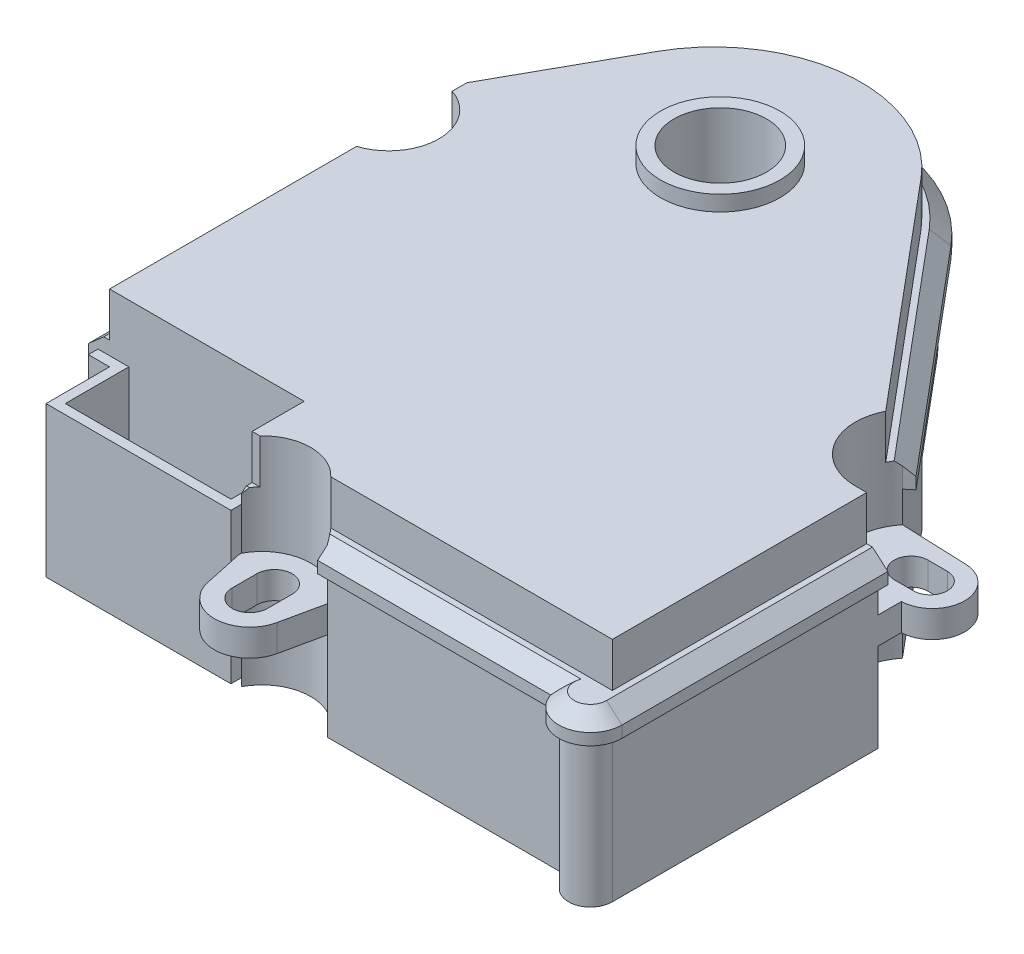
SolidWorks part; units mm, degrees
ref_plane "Front Plane" through (0, 0, 0) normal (0, 0, 1) x (1, 0, 0)
ref_plane "Top Plane" through (0, 0, 0) normal (0, 1, 0) x (1, 0, 0)
ref_plane "Right Plane" through (0, 0, 0) normal (1, 0, 0) x (0, 0, -1)
sketch "Sketch1" plane through (0, 0, 0) normal (0, 1, 0) x (1, 0, 0)
  line L0 (-34.65, 27.5) -> (-34.65, -27.5)
  line L1 (-34.65, -27.5) -> (34.65, -27.5)
  line L2 (40.35, -27.5) -> (40.35, 8.5)
  line L3 (40.35, 8.5) -> (8.1391, 46.8874)
  line L4 (-25.6622, 43.6579) -> (-34.65, 27.5)
  line L5 (-30.7563, 34.5) -> (18.5334, 34.5)
  line L6 (-7.65, 34.5) -> (-7.65, 54.25) construction
  circle A1 centre (-7.65, 34.5) radius 6
  circle A2 centre (-7.65, 34.5) radius 7.75
  arc A3 (40.35, -27.5) -> (34.65, -27.5) centre (37.5, -27.5) cw
  arc A4 (-25.6622, 43.6579) -> (8.1391, 46.8874) centre (-7.65, 33.6387) cw
  point P7 (0, -27.5)
  point P8 (-34.65, 0)
  dimension "D6" = 12
  dimension "D7" = 15.5
  dimension "D9" = 48
  dimension "D10" = 50
  dimension "D1" = 75
  dimension "D2" = 55
  dimension "D3" = 36
  dimension "D4" = 62
  dimension "D5" = 81.75
  dimension "D8" = 5.7
extrude "Boss-Extrude1" add sketch "Sketch1" along normal blind 28 contours A2 L6 A4 L4 L5 | L6 A2 L5 L3 A4 | A3 L2 L3 L5 A2 L4 L0 L1 region at (1.2938, 0, -1.2172) region at (-6.9972, 0, -43.3855)
extrude "Boss-Extrude2" add sketch "Sketch1<3>" along normal blind 2 and the other way up to surface from surface contours L6 A1 L5 A2 | L5 A2 A1 | A1 L6 A2 L5 region at (-12.0504, 0, -38.9004) region at (-14.525, 0, -34.3267) region at (-3.2496, 0, -38.9004) other way up to face at (3.954, 0, -7.1542) starting at face at (3.954, 28, -7.1542)
sketch "Sketch1<3>" plane through (0, 0, 0) normal (0, 1, 0) x (1, 0, 0) same geometry as "Sketch1"
extrude "Boss-Extrude3" add sketch "Sketch1<4>" against normal blind 6 contours L6 A1 L5 A2 | A1 L6 A2 L5 | L5 A2 A1 region at (-12.0504, 0, -38.9004) region at (-14.525, 0, -34.3267) region at (-3.2496, 0, -38.9004)
sketch "Sketch1<4>" plane through (0, 0, 0) normal (0, 1, 0) x (1, 0, 0) same geometry as "Sketch1"
extrude "Cut-Extrude1" cut sketch "Sketch1<5>" along normal blind 8 contours A2 L6 A4 L4 L5 | L6 A2 L5 L3 A4 region at (-6.9972, 0, -43.3855)
sketch "Sketch1<5>" plane through (0, 0, 0) normal (0, 1, 0) x (1, 0, 0) same geometry as "Sketch1"
sketch "Sketch6" plane through (0, 28, 0) normal (0, 1, 0) x (1, 0, 0)
  line L9 (38.85, -26) -> (38.85, 7.954)
  line L10 (38.85, 7.954) -> (6.9901, 45.9232)
  line L11 (-24.3514, 42.9288) -> (-33.15, 27.1109)
  line L12 (-33.15, 27.1109) -> (-33.15, -26)
  line L13 (-33.15, -26) -> (33.7821, -26)
  line L14 (-26.5361, 44.1441) -> (-35.65, 27.7594)
  line L15 (-35.65, 27.7594) -> (-35.65, -28.5)
  line L16 (-35.65, -28.5) -> (33.7821, -28.5)
  line L17 (41.35, -27.5) -> (41.35, 8.864)
  line L18 (41.35, 8.864) -> (8.9052, 47.5302)
  line L19 (-26.5361, 44.1441) -> (-35.65, 27.7594)
  line L20 (-35.65, 27.7594) -> (-35.65, -28.5)
  line L21 (-35.65, -28.5) -> (33.7821, -28.5)
  line L22 (41.35, -27.5) -> (41.35, 8.864)
  line L23 (41.35, 8.864) -> (8.9052, 47.5302)
  line L24 (-24.3514, 42.9288) -> (-33.4652, 26.5441) construction
  line L25 (-33.15, 27.7594) -> (-33.15, -26) construction
  line L26 (33.7821, -26) -> (38.85, -26)
  line L27 (38.85, -27.5) -> (38.85, 7.954) construction
  arc A3 (6.9901, 45.9232) -> (-24.3514, 42.9288) centre (-7.65, 33.6387) ccw
  arc A4 (8.9052, 47.5302) -> (-26.5361, 44.1441) centre (-7.65, 33.6387) ccw
  arc A5 (33.7821, -28.5) -> (41.35, -27.5) centre (37.5, -27.5) ccw
  arc A6 (8.9052, 47.5302) -> (-26.5361, 44.1441) centre (-7.65, 33.6387) ccw
  arc A7 (33.7821, -28.5) -> (41.35, -27.5) centre (37.5, -27.5) ccw
  arc A10 (36.1963, -27.8506) -> (38.85, -27.5) centre (37.5, -27.5) ccw construction
  dimension "D2" = 2.5
  dimension "D3" = 2.5
  dimension "D1" = 1
sketch "Sketch2" plane through (0, 28, 0) normal (0, 1, 0) x (1, 0, 0)
  line L0 (-34.65, -27.5) -> (34.65, -27.5) construction
  line L1 (40.35, -27.5) -> (40.35, 8.5) construction
  line L2 (-7.95, -27.5) -> (-6.7974, -32.866)
  line L3 (2.1974, -32.866) -> (3.35, -27.5)
  line L4 (-4.6, -28.7) -> (-4.6, -31.9)
  line L5 (0, -31.9) -> (0, -28.7)
  arc A1 (-6.7974, -32.866) -> (2.1974, -32.866) centre (-2.3, -31.9) ccw
  arc A2 (-4.6, -31.9) -> (0, -31.9) centre (-2.3, -31.9) ccw
  arc A3 (0, -28.7) -> (-4.6, -28.7) centre (-2.3, -28.7) ccw
  arc A4 (-7.95, -27.5) -> (3.35, -27.5) centre (-2.3, -30.3104) cw
  point P18 (-2.3, -26.4)
  point P19 (-2.3, -34.2)
  point P20 (-2.3, -36.5)
  point P21 (-2.3, -24)
  line M7 (-34.65, -27.5) -> (34.65, -27.5)
  dimension "D3" = 7.8
  dimension "D5" = 2.3
  dimension "D6" = 9
  dimension "D1" = 37
  dimension "D2" = 11.3
  dimension "D4" = 4.6
  dimension "D7" = 12.5
extrude "Cut-Extrude2" cut sketch "Sketch2" against normal through all contours A4 A3 M7 | A3 M7 region at (-2.3, 28, 25.9407) region at (-2.3, 28, 27.0495)
extrude "Boss-Extrude4" add sketch "Sketch2<3>" against normal offset from surface (3.5 mm away) 11.5 from offset 13 up to face at (1.2661, 0, -2.6727) offset against normal yes
sketch "Sketch2<3>" plane through (0, 28, 0) normal (0, 1, 0) x (1, 0, 0) same geometry as "Sketch2"
sketch "Sketch3" plane through (0, 28, 0) normal (0, 1, 0) x (1, 0, 0)
  line L0 (-34.65, 27.5) -> (-34.65, -27.5) construction
  line L1 (-34.65, 25.5) -> (-37.978, 22.6409)
  line L2 (-37.978, 15.3591) -> (-34.65, 12.5)
  arc A0 (-34.65, 25.5) -> (-34.65, 12.5) centre (-35.1708, 19) cw
  arc A1 (-37.978, 22.6409) -> (-37.978, 15.3591) centre (-34.85, 19) ccw
  circle A2 centre (-34.85, 19) radius 2.6
  point P22 (-28.65, 19)
  point P23 (-39.65, 19)
  line M9 (-34.65, 27.5) -> (-34.65, -27.5)
  dimension "D1" = 5.2
  dimension "D2" = 2.2
  dimension "D4" = 2
  dimension "D3" = 13
  dimension "D5" = 11
  dimension "D6" = 5
extrude "Cut-Extrude4" cut sketch "Sketch3" against normal through all contours A2 M9 | A2 A0 M9 region at (-31.8314, 28, -19) region at (-33.6377, 28, -19)
extrude "Boss-Extrude5" add sketch "Sketch3<3>" against normal blind 3.5 from offset 13 offset against normal yes
sketch "Sketch3<3>" plane through (0, 28, 0) normal (0, 1, 0) x (1, 0, 0) same geometry as "Sketch3"
sketch "Sketch4" plane through (0, 28, 0) normal (0, 1, 0) x (1, 0, 0)
  line L0 (40.35, 8.5) -> (8.1391, 46.8874) construction
  line L1 (37.3759, 7) -> (40.35, 7)
  line L2 (3.35, -27.5) -> (34.65, -27.5) construction
  line L4 (40.35, 18.3702) -> (31.7888, 18.7028)
  line L5 (37.4257, 16.3851) -> (39.9257, 16.3851)
  line L6 (39.9257, 11.9851) -> (37.4257, 11.9851)
  line L7 (40.35, -27.5) -> (40.35, 8.5) construction
  line L8 (40.35, 7) -> (40.35, 10)
  arc A0 (31.7888, 18.7028) -> (37.3759, 7) centre (37.3759, 14.1851) ccw
  arc A1 (40.35, 10) -> (40.35, 18.3702) centre (40.1874, 14.1851) ccw
  arc A2 (39.9257, 16.3851) -> (39.9257, 11.9851) centre (39.9257, 14.1851) cw
  arc A3 (37.4257, 11.9851) -> (37.4257, 16.3851) centre (37.4257, 14.1851) cw
  point P12 (42.1257, 14.1851)
  point P17 (44.3757, 14.1851)
  point P26 (35.2257, 14.1851)
  line M13 (40.35, -27.5) -> (40.35, 8.5)
  line M14 (40.35, 8.5) -> (8.1391, 46.8874)
  dimension "D6" = 4.4
  dimension "D7" = 2.25
  dimension "D1" = 34.5
  dimension "D2" = 14.5
  dimension "D4" = 6.9
  dimension "D5" = 3
extrude "Cut-Extrude5" cut sketch "Sketch4" against normal through all contours A3 M14 | A3 A0 M14 M13 region at (34.4424, 28, -11.6642) region at (36.0974, 28, -13.0706)
extrude "Boss-Extrude6" add sketch "Sketch4<3>" against normal blind 3.5 from offset 13 offset against normal yes
sketch "Sketch4<3>" plane through (0, 28, 0) normal (0, 1, 0) x (1, 0, 0) same geometry as "Sketch4"
extrude "Cut-Extrude6" cut sketch "Sketch6" against normal blind 5.75
sketch "Sketch7" plane through (0, 22.25, 0) normal (0, 1, 0) x (1, 0, 0)
  line L8 (2.3088, -26) -> (38.85, -26)
  line L9 (2.3088, -26) -> (38.85, -26)
  line L10 (38.85, 7) -> (37.3759, 7)
  line L11 (38.85, -26) -> (38.85, 7)
  line L12 (-34.65, 12.5) -> (-34.65, -27.5) construction
  line L13 (-34.65, -27.5) -> (-7.95, -27.5) construction
  line L14 (3.35, -27.5) -> (34.65, -27.5) construction
  line L15 (40.35, -27.5) -> (40.35, 7) construction
  line L16 (37.3759, 7) -> (40.35, 7) construction
  line L17 (31.7888, 18.7028) -> (8.1391, 46.8874) construction
  line L18 (-25.6622, 43.6579) -> (-34.65, 27.5) construction
  line L19 (-34.65, 27.5) -> (-34.65, 25.5) construction
  line L20 (-34.65, 12.5) -> (-34.65, -27.5)
  line L21 (-34.65, -27.5) -> (-7.95, -27.5)
  line L22 (3.35, -27.5) -> (34.65, -27.5)
  line L23 (40.35, -27.5) -> (40.35, 7)
  line L24 (37.3759, 7) -> (40.35, 7)
  line L25 (31.7888, 18.7028) -> (8.1391, 46.8874)
  line L26 (-25.6622, 43.6579) -> (-34.65, 27.5)
  line L27 (-34.65, 27.5) -> (-34.65, 25.5)
  line L28 (-35.9, 12.5) -> (-35.9, -28.75)
  line L29 (-35.9, -28.75) -> (-7.95, -28.75)
  line L30 (3.35, -28.75) -> (33.5952, -28.75)
  line L31 (41.6, -27.5) -> (41.6, 7)
  line L32 (32.7464, 19.5063) -> (9.0967, 47.6909)
  line L33 (-26.7546, 44.2656) -> (-35.9, 27.8243)
  line L34 (-35.9, 27.8243) -> (-35.9, 25.5)
  line L35 (-35.9, 25.5) -> (-34.65, 25.5)
  line L36 (-34.65, 12.5) -> (-35.9, 12.5)
  line L37 (-7.95, -28.75) -> (-7.95, -27.5)
  line L38 (3.35, -28.75) -> (3.35, -27.5)
  line L39 (41.6, 7) -> (40.35, 7)
  line L40 (32.7464, 19.5063) -> (31.7888, 18.7028)
  line L41 (38.85, -26) -> (38.85, 7)
  line L42 (30.9404, 17.3803) -> (6.9901, 45.9232)
  line L43 (30.9404, 17.3803) -> (6.9901, 45.9232)
  line L44 (-24.3514, 42.9288) -> (-33.15, 27.1109)
  line L47 (38.85, 7) -> (37.3759, 7)
  line L53 (-24.3514, 42.9288) -> (-33.15, 27.1109)
  line L54 (-33.15, 27.1109) -> (-33.15, 25.1998)
  line L55 (-33.15, 27.1109) -> (-33.15, 25.1998)
  line L56 (-33.15, 12.8002) -> (-33.15, -26)
  line L57 (-33.15, 12.8002) -> (-33.15, -26)
  line L58 (-33.15, -26) -> (-6.9088, -26)
  line L59 (-33.15, -26) -> (-6.9088, -26)
  arc A4 (30.9404, 17.3803) -> (37.3759, 7) centre (37.3759, 14.1851) ccw
  arc A5 (6.9901, 45.9232) -> (-24.3514, 42.9288) centre (-7.65, 33.6387) ccw
  arc A6 (-33.15, 12.8002) -> (-33.15, 25.1998) centre (-35.1708, 19) ccw
  arc A7 (2.3088, -26) -> (-6.9088, -26) centre (-2.3, -30.3104) ccw
  arc A8 (3.35, -27.5) -> (-7.95, -27.5) centre (-2.3, -30.3104) ccw construction
  arc A9 (34.65, -27.5) -> (40.35, -27.5) centre (37.5, -27.5) ccw construction
  arc A10 (31.7888, 18.7028) -> (37.3759, 7) centre (37.3759, 14.1851) ccw construction
  arc A11 (8.1391, 46.8874) -> (-25.6622, 43.6579) centre (-7.65, 33.6387) ccw construction
  arc A12 (-34.65, 12.5) -> (-34.65, 25.5) centre (-35.1708, 19) ccw construction
  arc A13 (3.35, -27.5) -> (-7.95, -27.5) centre (-2.3, -30.3104) ccw
  arc A14 (34.65, -27.5) -> (40.35, -27.5) centre (37.5, -27.5) ccw
  arc A15 (31.7888, 18.7028) -> (37.3759, 7) centre (37.3759, 14.1851) ccw
  arc A16 (8.1391, 46.8874) -> (-25.6622, 43.6579) centre (-7.65, 33.6387) ccw
  arc A17 (-34.65, 12.5) -> (-34.65, 25.5) centre (-35.1708, 19) ccw
  arc A18 (33.5952, -28.75) -> (41.6, -27.5) centre (37.5, -27.5) ccw
  arc A19 (9.0967, 47.6909) -> (-26.7546, 44.2656) centre (-7.65, 33.6387) ccw
  arc A20 (30.9404, 17.3803) -> (37.3759, 7) centre (37.3759, 14.1851) ccw
  arc A22 (-33.15, 12.8002) -> (-33.15, 25.1998) centre (-35.1708, 19) ccw
  arc A23 (2.3088, -26) -> (-6.9088, -26) centre (-2.3, -30.3104) ccw
  arc A24 (6.9901, 45.9232) -> (-24.3514, 42.9288) centre (-7.65, 33.6387) ccw
  line M13 (-34.65, 12.5) -> (-34.65, -27.5)
  line M14 (-34.65, -27.5) -> (-7.95, -27.5)
  arc M15 (-7.95, -27.5) -> (-6.9088, -26) centre (-2.3, -30.3104) cw
  line M16 (-6.9088, -26) -> (-33.15, -26)
  line M17 (-33.15, -26) -> (-33.15, 12.8002)
  arc M18 (-33.15, 12.8002) -> (-34.65, 12.5) centre (-35.1708, 19) cw
  dimension "D1" = 1.25
  dimension "D2" = 0
extrude "Boss-Extrude8" add sketch "Sketch7" against normal offset from surface (3.25 mm away) 19 contours L32 A19 L33 L34 L35 L27 L26 A16 L25 L40 | A24 L43 A15 L25 A16 L26 L27 A17 L55 L53 | L30 A18 L31 L39 L23 A14 L22 L38 | L22 A14 L23 L24 L41 L9 A13 | M18 M13 M14 M15 M16 M17 | L29 L37 L36 L28 M14 M13 region at (20.5794, 22.25, 26.5331) region at (-7.8859, 22.25, 26.4332) region at (19, 22.25, 28.0434) region at (-8.4483, 22.25, 28.125) region at (19.5473, 22.25, -32.1402) region at (20.5606, 22.25, -33.2958) up to face at (1.0734, 0, -5.9894)
chamfer "Chamfer1" distance 1.75 distance2 2 9 edges at (18.4726, 22.25, 28.75) (38.1326, 22.25, 31.5509) (41.6, 22.25, 10.25) (20.9215, 22.25, -33.5986) (-9.7292, 22.25, -55.4009) (-31.3273, 22.25, -36.0449) (-35.9, 22.25, -26.6621) (-21.925, 22.25, 28.75) (-35.9, 22.25, 8.125) first distance on face at (18.4726, 20.625, 28.75) first distance on face at (37.8651, 20.625, 29.838) first distance on face at (41.6, 20.625, 10.25) first distance on face at (20.9215, 20.625, -33.5986) first distance on face at (-9.2791, 20.625, -50.6896) first distance on face at (-31.3273, 20.625, -36.0449) first distance on face at (-35.9, 20.625, -26.6621) first distance on face at (-21.925, 20.625, 28.75) first distance on face at (-35.9, 20.625, 8.125)
sketch "Sketch8" plane through (0, -6, 0) normal (0, -1, 0) x (1, 0, 0)
  line L0 (-10.9666, -29.5) -> (-4.3334, -29.5)
  line L1 (-15.4, -34.5) -> (0.1, -34.5) construction
  line L2 (-10.9666, -39.5) -> (-4.3334, -39.5)
  circle A0 centre (-7.65, -34.5) radius 6 construction
  circle A1 centre (-7.65, -34.5) radius 7.75 construction
  arc A2 (-10.9666, -29.5) -> (-4.3334, -29.5) centre (-7.65, -34.5) cw
  arc A3 (-10.9666, -39.5) -> (-4.3334, -39.5) centre (-7.65, -34.5) ccw
  dimension "D1" = 10
extrude "Boss-Extrude9" add sketch "Sketch8" against normal blind 12.5
sketch "Sketch9" plane through (0, 6.5, 0) normal (0, 1, 0) x (1, 0, 0)
  line L0 (-15.4, 34.5) -> (0.1, 34.5) construction
  line L1 (-10.9666, 29.5) -> (-4.3334, 29.5) construction
  circle A0 centre (-7.65, 34.5) radius 7.75 construction
  circle A1 centre (-7.65, 34.5) radius 7.75 construction
  circle A2 centre (-7.65, 34.5) radius 5
  circle A3 centre (-7.65, 34.5) radius 6
  circle A4 centre (-7.65, 34.5) radius 6 construction
  point P12 (-7.65, 29.5)
extrude "Boss-Extrude10" add sketch "Sketch9" along normal blind 5
sketch "Sketch10" plane through (0, 0, 0) normal (0, 1, 0) x (1, 0, 0)
  line L0 (-34.65, 12.5) -> (-34.65, -27.5) construction
  line L1 (-31.9, -19.25) -> (-7.9, -19.25)
  line L2 (-31.9, -19.25) -> (-31.9, -28.75)
  line L3 (-31.9, -28.75) -> (-7.9, -28.75)
  line L4 (-7.9, -19.25) -> (-7.9, -28.75)
  line L6 (-31.9, -28.75) -> (-35.9, -28.75)
  line L7 (-35.9, -28.75) -> (-35.9, -19.25)
  line L9 (-35.9, -19.25) -> (-31.9, -19.25)
  line L10 (-35.9, -20.5) -> (-31.9, -20.5)
  line L12 (-34.65, -27.5) -> (-7.95, -27.5) construction
  line L14 (-35.9, -28.75) -> (-35.9, 12.5) construction
  line L15 (-34.65, -19.25) -> (-34.65, -20.5)
  dimension "D1" = 9.5
  dimension "D2" = 24
  dimension "D3" = 2.75
  dimension "D4" = 1.25
  dimension "D5" = 1.25
  dimension "D6" = 1.25
extrude "Boss-Extrude11" add sketch "Sketch10" along normal blind 25 contours L4 L1 L2 L3 region at (-19.9, 0, 24)
extrude "Cut-Extrude7" cut sketch "Sketch10<3>" against normal blind 7.5 from surface contours L4 L1 L2 L3 | L7 L10 L2 L9 | L10 L7 L6 L2 | L9 L15 L10 L2 region at (-19.9, 0, 24) region at (-33.275, 0, 19.875) region at (-33.9, 0, 24.625) region at (-35.275, 0, 19.875) starting at face at (-7.65, 28, -26.75)
sketch "Sketch10<3>" plane through (0, 0, 0) normal (0, 1, 0) x (1, 0, 0) same geometry as "Sketch10"
extrude "Cut-Extrude8" cut sketch "Sketch10<4>" along normal through all contours L10 L7 L6 L2 | L15 L9 L7 L10 region at (-33.9, 0, 24.625) region at (-35.275, 0, 19.875)
sketch "Sketch10<4>" plane through (0, 0, 0) normal (0, 1, 0) x (1, 0, 0) same geometry as "Sketch10"
sketch "Sketch11" plane through (0, 0, 0) normal (0, -1, 0) x (1, 0, 0)
  line L0 (-34.65, 20.5) -> (-31.9, 20.5) construction
  line L1 (-31.9, 28.75) -> (-7.9, 28.75)
  line L2 (-31.9, 28.75) -> (-31.9, 20.5)
  line L3 (-31.9, 20.5) -> (-7.9, 20.5)
  line L4 (-7.9, 28.75) -> (-7.9, 20.5)
  line L5 (-7.9, 27.4016) -> (-7.9, 28.75) construction
extrude "Cut-Extrude10" cut sketch "Sketch11" against normal blind 1
sketch "Sketch12" plane through (0, 20.5, 0) normal (0, 1, 0) x (1, 0, 0)
  line L0 (-7.9, -19.25) -> (-33.15, -19.25) construction
  line L1 (-30.65, -19.25) -> (-9.15, -19.25)
  line L2 (-30.65, -19.25) -> (-30.65, -27.5)
  line L3 (-30.65, -27.5) -> (-9.15, -27.5)
  line L4 (-9.15, -19.25) -> (-9.15, -27.5)
  line L5 (-31.9, -20.5) -> (-31.9, -28.75) construction
  line L6 (-7.9, -28.75) -> (-31.9, -28.75) construction
  line L8 (-7.9, -27.4016) -> (-7.9, -19.25) construction
  dimension "D1" = 1.25
  dimension "D2" = 1.25
  dimension "D3" = 1.25
extrude "Cut-Extrude11" cut sketch "Sketch12" against normal blind 15
